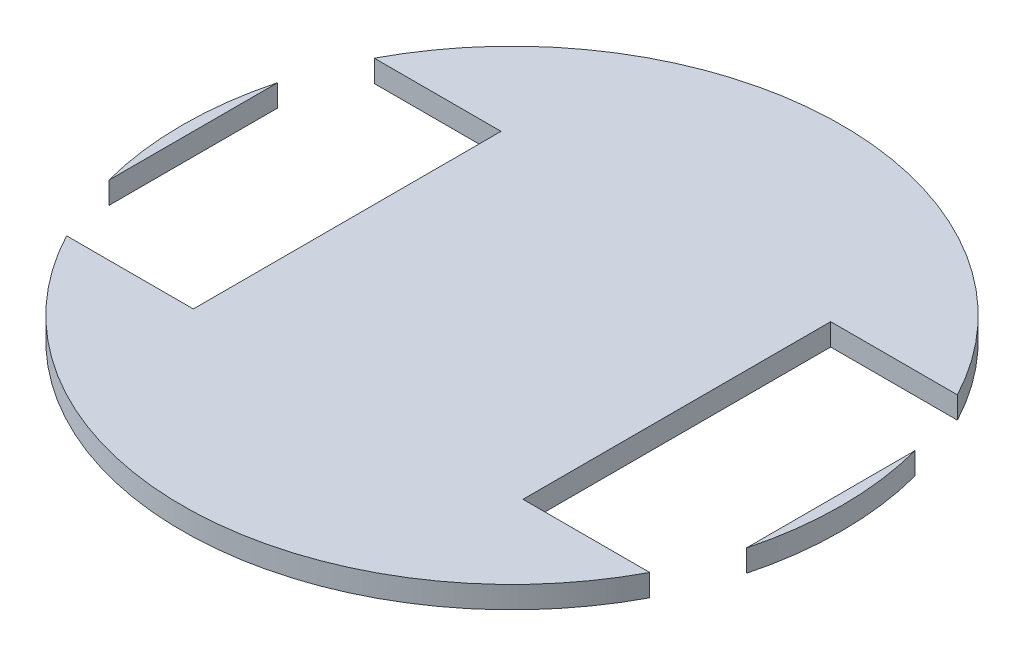
SolidWorks part; units mm, degrees
ref_plane "Front Plane" through (0, 0, 0) normal (0, 0, 1) x (1, 0, 0)
ref_plane "Top Plane" through (0, 0, 0) normal (0, 1, 0) x (1, 0, 0)
ref_plane "Right Plane" through (0, 0, 0) normal (1, 0, 0) x (0, 0, -1)
sketch "Sketch1" plane through (0, 0, 0) normal (0, 1, 0) x (1, 0, 0)
  circle A0 centre (0, 0) radius 75
  point P3 (0, 0)
  dimension "D1" = 150
extrude "Boss-Extrude2" add sketch "Sketch1" along normal blind 5 contours A0
sketch "Sketch5" plane through (0, 5, 0) normal (0, 1, 0) x (1, 0, 0)
  line L0 (0, 0) -> (162.2631, 0) construction
  line L1 (0, 0) -> (0, 110.711) construction
  line L2 (37.5, 35) -> (72.5, 35)
  line L3 (37.5, 35) -> (37.5, -35)
  line L4 (37.5, -35) -> (72.5, -35)
  line L5 (72.5, 35) -> (72.5, -35)
  line L6 (37.5, 35) -> (72.5, -35) construction
  line L7 (37.5, -35) -> (72.5, 35) construction
  line L8 (-72.5, 35) -> (-72.5, -35)
  line L9 (-37.5, -35) -> (-72.5, -35)
  line L10 (-37.5, 35) -> (-37.5, -35)
  line L11 (-37.5, 35) -> (-72.5, 35)
  point P3 (55, 0)
  dimension "D1" = 70
  dimension "D2" = 35
  dimension "D3" = 55
extrude "Cut-Extrude1" cut sketch "Sketch5" against normal through all
